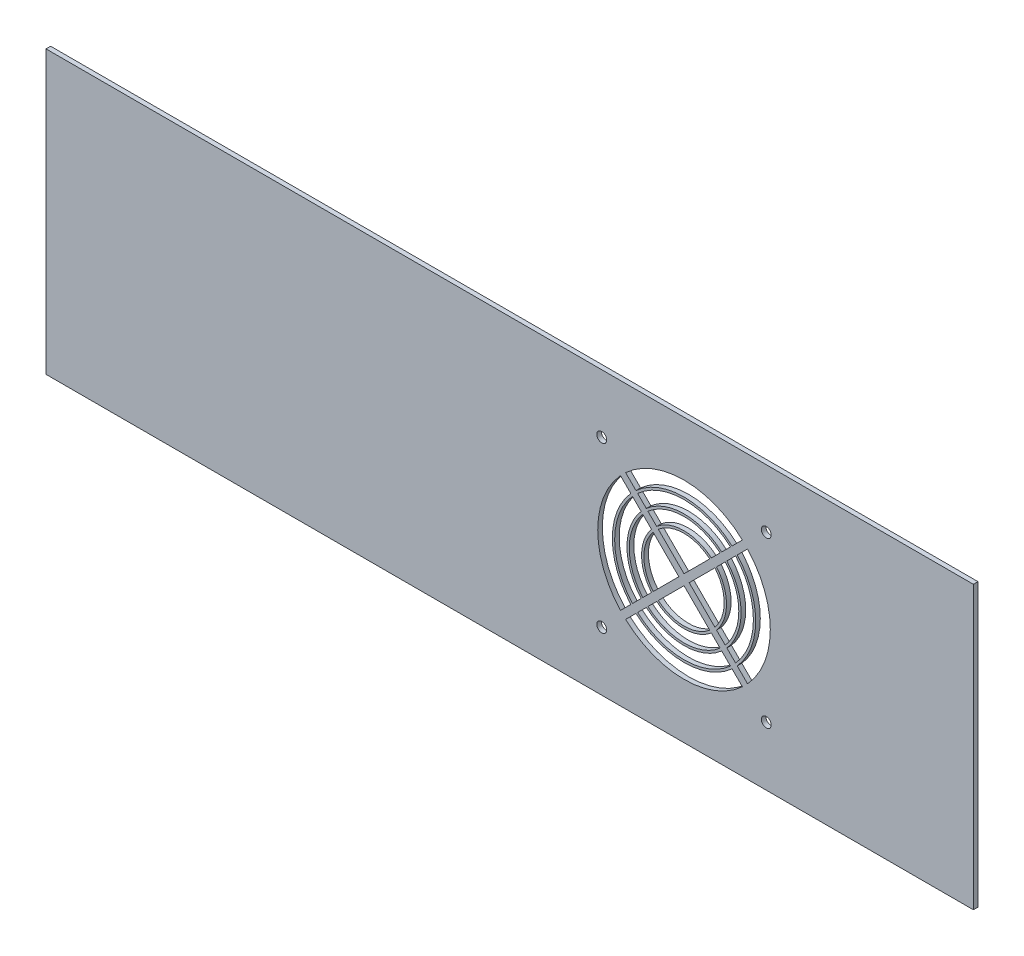
SolidWorks part; units mm, degrees
ref_plane "Front Plane" through (0, 0, 0) normal (0, 0, 1) x (1, 0, 0)
ref_plane "Top Plane" through (0, 0, 0) normal (0, 1, 0) x (1, 0, 0)
ref_plane "Right Plane" through (0, 0, 0) normal (1, 0, 0) x (0, 0, -1)
sketch "Sketch1" plane through (0, 0, 0) normal (0, 0, 1) x (1, 0, 0)
  line L0 (302.6205, -33.535) -> (249.6345, -86.5199)
  line L1 (0, 0) -> (403, 0)
  line L2 (0, 0) -> (0, -122.5)
  line L3 (0, -122.5) -> (403, -122.5)
  line L4 (403, 0) -> (403, -122.5)
  line L5 (304.8655, -35.7801) -> (251.8795, -88.765)
  line L6 (277.25, -59.5625) -> (277.25, -62.7375) construction
  line L7 (275.6625, -61.15) -> (278.8375, -61.15) construction
  line L8 (277.25, -61.15) -> (303.7665, -34.6335) construction
  line L9 (251.8801, -33.5345) -> (304.865, -86.5205)
  line L10 (302.6199, -88.7655) -> (249.635, -35.7795)
  circle A0 centre (241.5, -25.4) radius 2.15
  circle A1 centre (313, -25.4) radius 2.15
  circle A2 centre (313, -96.9) radius 2.15
  circle A3 centre (241.5, -96.9) radius 2.15
  circle A4 centre (277.25, -61.15) radius 37.5
  arc A5 (298.1254, -38.0299) -> (256.375, -38.0295) centre (277.25, -61.15) ccw
  arc A6 (293.6279, -42.5273) -> (260.8724, -42.527) centre (277.25, -61.15) ccw
  arc A7 (289.1253, -47.0298) -> (265.3749, -47.0296) centre (277.25, -61.15) ccw
  circle A8 centre (277.25, -61.15) radius 1.5875
  arc A9 (297.4174, -38.738) -> (257.083, -38.7376) centre (277.25, -61.15) ccw
  arc A10 (288.4154, -47.7397) -> (266.0848, -47.7395) centre (277.25, -61.15) ccw
  arc A11 (292.9193, -43.236) -> (261.581, -43.2357) centre (277.25, -61.15) ccw
  arc A12 (254.1299, -40.2746) -> (254.1295, -82.025) centre (277.25, -61.15) ccw
  arc A13 (254.838, -40.9826) -> (254.8376, -81.317) centre (277.25, -61.15) ccw
  arc A14 (258.6273, -44.7721) -> (258.627, -77.5276) centre (277.25, -61.15) ccw
  arc A15 (259.336, -45.4807) -> (259.3357, -76.819) centre (277.25, -61.15) ccw
  arc A16 (263.1298, -49.2747) -> (263.1296, -73.0251) centre (277.25, -61.15) ccw
  arc A17 (263.8397, -49.9846) -> (263.8395, -72.3152) centre (277.25, -61.15) ccw
  arc A18 (256.3746, -84.2701) -> (298.125, -84.2705) centre (277.25, -61.15) ccw
  arc A19 (257.0826, -83.562) -> (297.417, -83.5624) centre (277.25, -61.15) ccw
  arc A20 (260.8721, -79.7727) -> (293.6276, -79.773) centre (277.25, -61.15) ccw
  arc A21 (261.5807, -79.064) -> (292.919, -79.0643) centre (277.25, -61.15) ccw
  arc A22 (265.3747, -75.2702) -> (289.1251, -75.2704) centre (277.25, -61.15) ccw
  arc A23 (266.0846, -74.5603) -> (288.4152, -74.5605) centre (277.25, -61.15) ccw
  arc A24 (300.3701, -82.0254) -> (300.3705, -40.275) centre (277.25, -61.15) ccw
  arc A25 (299.662, -81.3174) -> (299.6624, -40.983) centre (277.25, -61.15) ccw
  arc A26 (295.8727, -77.5279) -> (295.873, -44.7724) centre (277.25, -61.15) ccw
  arc A27 (295.164, -76.8193) -> (295.1643, -45.481) centre (277.25, -61.15) ccw
  arc A28 (291.3702, -73.0253) -> (291.3704, -49.2749) centre (277.25, -61.15) ccw
  arc A29 (290.6603, -72.3154) -> (290.6605, -49.9848) centre (277.25, -61.15) ccw
  dimension "D5" = 4.3
  dimension "D9" = 75
  dimension "D15" = 3.175
  dimension "D1" = 403
  dimension "D2" = 122.5
  dimension "D3" = 71.5
  dimension "D4" = 71.5
  dimension "D6" = 90
  dimension "D7" = 25.4
  dimension "D8" = 35.75
  dimension "D10" = 35.75
  dimension "D11" = 6.35
  dimension "D12" = 6.35
  dimension "D13" = 6.35
  dimension "D14" = 3.175
  dimension "D16" = 1.5875
  dimension "D17" = 45
  dimension "D18" = 1
  dimension "D19" = 1
  dimension "D20" = 1
  dimension "D21" = 3.175
extrude "Boss-Extrude1" add sketch "Sketch1" along normal blind 2 contours L4 L1 L2 L3 A4 A3 A2 A1 A0 | L5 A4 L0 L9 | L10 A4 L9 L5 | L9 A4 L10 L0 | L0 A4 L5 L10 | A8 L10 L5 | A8 L9 L0 | A8 | A8 L0 L10 | A8 L5 L9 | A29 L9 A28 L5 | A25 L9 A24 L5 | A9 L0 A5 L9 | A11 L0 A6 L9 | A10 L0 A7 L9 | A27 L9 A26 L5 | A23 L5 A22 L10 | A17 L10 A16 L0 | A15 L10 A14 L0 | A13 L10 A12 L0 | A21 L5 A20 L10 | A19 L5 A18 L10 region at (291.0657, -47.3346, 0) region at (297.4698, -38.0823, 0) region at (263.4346, -47.3343, 0) region at (307.9734, -61.1503, 0) region at (293.0369, -42.645, 0) region at (291.0654, -74.9657, 0) region at (254.1823, -40.9302, 0) region at (263.4343, -74.9654, 0) region at (301.7153, -61.1502, 0) region at (288.5987, -47.2131, 0) region at (277.2497, -91.8734, 0) region at (258.745, -45.3631, 0) region at (295.4572, -61.1502, 0) region at (277.25, -59.4064, 0) region at (277.2498, -85.6153, 0) region at (263.3131, -49.8013, 0) region at (275.5064, -61.15, 0) region at (277.25, -61.15, 0) region at (278.9936, -61.15, 0) region at (277.25, -62.8936, 0) region at (277.2498, -79.3572, 0) region at (193.9473, -61.26, 0)
equation "\"D4@Sketch1\"=\"D3@Sketch1\""
equation "\"D8@Sketch1\"=\"D3@Sketch1\"/2"
equation "\"D10@Sketch1\"=\"D4@Sketch1\"/2"
equation "\"D12@Sketch1\"=\"D11@Sketch1\""
equation "\"D13@Sketch1\"=\"D11@Sketch1\""
equation "\"D15@Sketch1\"=\"D14@Sketch1\""
equation "\"D16@Sketch1\"=\"D15@Sketch1\"/2"
equation "\"D21@Sketch1\"=\"D14@Sketch1\""
